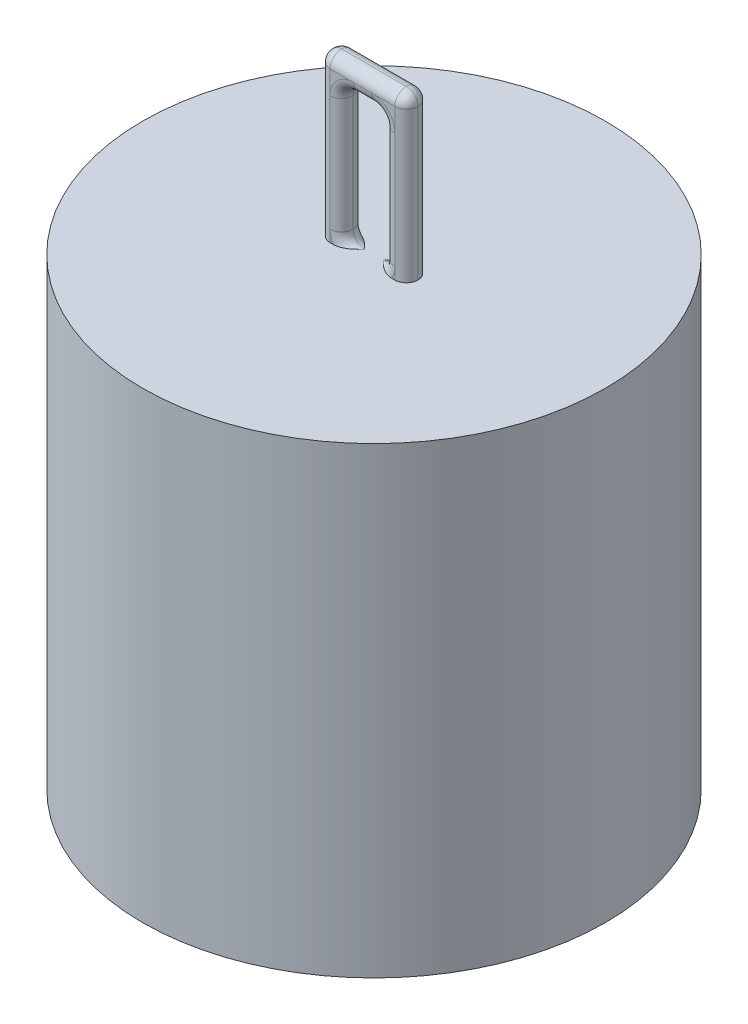
SolidWorks part; units mm, degrees
material "Plain Carbon Steel"
ref_plane "Front Plane" through (0, 0, 0) normal (0, 0, 1) x (1, 0, 0)
ref_plane "Top Plane" through (0, 0, 0) normal (0, 1, 0) x (1, 0, 0)
ref_plane "Right Plane" through (0, 0, 0) normal (1, 0, 0) x (0, 0, -1)
sketch "Sketch1" plane through (0, 0, 0) normal (0, 0, 1) x (1, 0, 0)
  line L0 (0, 0) -> (0, 25) construction
  line L1 (-95, 25) -> (95, 25)
  line L2 (-95, 25) -> (-95, -375)
  line L3 (-95, -375) -> (95, -375)
  line L4 (95, 25) -> (95, -375)
  line L5 (-45, -25) -> (45, -25)
  line L6 (-45, -25) -> (-45, -325)
  line L7 (-45, -325) -> (45, -325)
  line L8 (45, -25) -> (45, -325)
  dimension "D1" = 25
  dimension "D2" = 50
  dimension "D3" = 400
  dimension "D4" = 190
  dimension "D5" = 50
  dimension "D6" = 50
  dimension "D7" = 50
extrude "Boss-Extrude1" add sketch "Sketch1" along normal mid plane 50
fillet "Fillet1" radius 25 16 edges at (-45, -175, -25) (0, -25, -25) (0, -325, -25) (45, -175, 25) (45, -175, -25) (0, -375, 25) (95, -175, 25) (95, -175, -25) (0, -375, -25) (-95, -175, -25) (0, 25, -25) (0, -325, 25) (-45, -175, 25) (-95, -175, 25) (0, -25, 25) (0, 25, 25)
ref_plane "Plane2" through (0, -325, 0) normal (0, 1, 0) x (1, 0, 0)
sketch "Sketch2" plane through (0, -325, 0) normal (0, 1, 0) x (1, 0, 0)
  line L0 (-20, 0) -> (20, 0) construction
  line L1 (-20, 0) -> (20, 0) construction
  circle A0 centre (0, 0) radius 500
  dimension "D1" = 1000
extrude "Boss-Extrude2" add sketch "Sketch2" against normal blind 1000 contours A0
